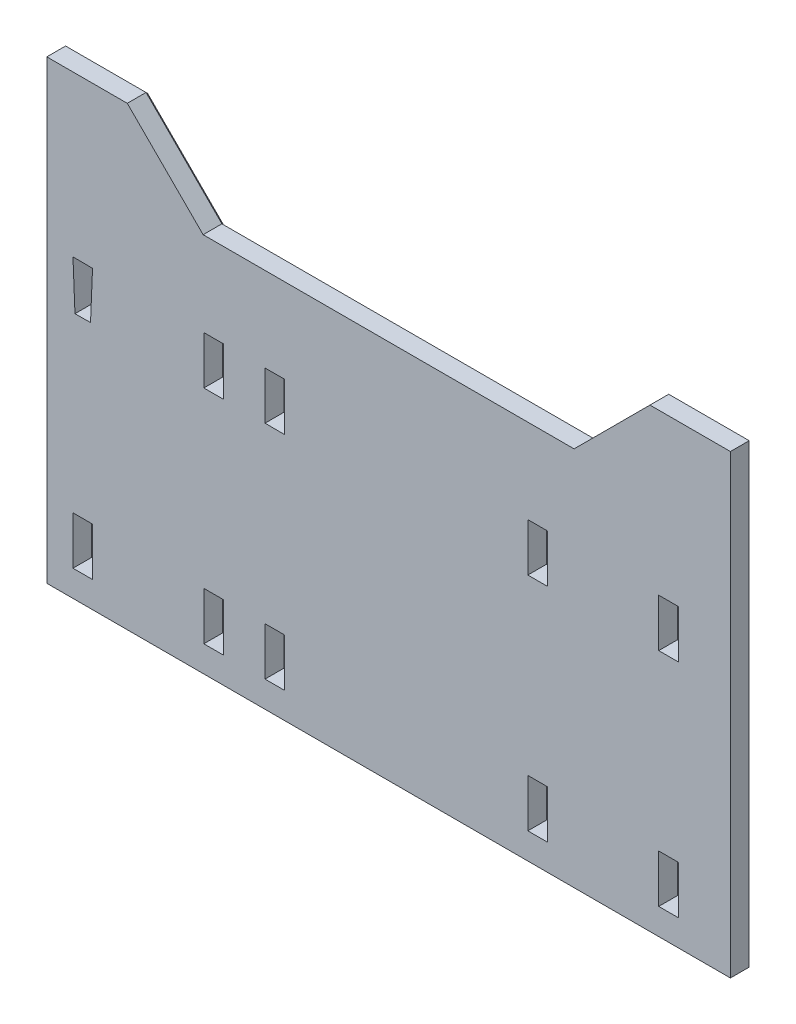
SolidWorks part; units mm, degrees
ref_plane "Front Plane" through (0, 0, 0) normal (0, 0, 1) x (1, 0, 0)
ref_plane "Top Plane" through (0, 0, 0) normal (0, 1, 0) x (1, 0, 0)
ref_plane "Right Plane" through (0, 0, 0) normal (1, 0, 0) x (0, 0, -1)
sketch "Sketch1" plane through (0, 0, 0) normal (0, 0, 1) x (1, 0, 0)
  line L6 (-34.4451, 25.1249) -> (-30.7951, 25.1249)
  line L7 (25.9549, 25.1249) -> (29.6049, 25.1249)
  line L8 (25.9549, 25.1249) -> (25.9549, 16.1751)
  line L9 (25.9549, 16.1751) -> (29.6049, 16.1751)
  line L10 (29.6049, 25.1249) -> (29.6049, 16.1751)
  line L12 (25.9549, -16.1751) -> (29.6049, -16.1751)
  line L13 (25.9549, -25.1249) -> (25.9549, -16.1751)
  line L14 (29.6049, -25.1249) -> (29.6049, -16.1751)
  line L15 (25.9549, -25.1249) -> (29.6049, -25.1249)
  line L16 (-19.3951, 25.1249) -> (-23.0451, 25.0989)
  line L17 (-19.3951, 25.1249) -> (-19.408, 16.1751)
  line L18 (-23.0451, 25.0989) -> (-23.0322, 16.2011)
  line L19 (-19.408, 16.1751) -> (-23.0322, 16.2011)
  line L20 (-19.3951, -16.1751) -> (-23.0451, -16.1751)
  line L21 (-19.3951, -25.1249) -> (-19.3951, -16.1751)
  line L22 (-23.0451, -25.1249) -> (-23.0451, -16.1751)
  line L23 (-19.3951, -25.1249) -> (-23.0451, -25.1249)
  line L39 (50.3549, 25.1249) -> (54.0049, 25.1249)
  line L40 (50.3549, 25.1249) -> (50.3549, 16.1751)
  line L41 (50.3549, 16.1751) -> (54.0049, 16.1751)
  line L42 (54.0049, 25.1249) -> (54.0049, 16.1751)
  line L43 (50.3549, -16.1751) -> (54.0049, -16.1751)
  line L44 (50.3549, -16.1751) -> (50.3549, -25.1249)
  line L45 (50.3549, -25.1249) -> (54.0049, -25.1249)
  line L46 (54.0049, -16.1751) -> (54.0049, -25.1249)
  line L47 (-34.4451, 25.1249) -> (-34.4451, 16.1751)
  line L48 (-34.4451, 16.1751) -> (-30.7951, 16.1751)
  line L49 (-30.7951, 25.1249) -> (-30.7951, 16.1751)
  line L50 (-34.4451, -16.1751) -> (-30.7951, -16.1751)
  line L51 (-34.4451, -16.1751) -> (-34.4451, -25.1249)
  line L52 (-34.4451, -25.1249) -> (-30.7951, -25.1249)
  line L53 (-30.7951, -16.1751) -> (-30.7951, -25.1249)
  line L60 (-58.8451, 25.1461) -> (-55.1951, 25.121)
  line L61 (-58.8451, 25.1461) -> (-58.4713, 16.1539)
  line L62 (-58.4713, 16.1539) -> (-55.5689, 16.179)
  line L63 (-55.1951, 25.121) -> (-55.5689, 16.179)
  line L64 (-58.8451, -16.1751) -> (-55.1951, -16.1751)
  line L65 (-58.8451, -16.1751) -> (-58.8451, -25.1249)
  line L66 (-58.8451, -25.1249) -> (-55.1951, -25.1249)
  line L67 (-55.1951, -16.1751) -> (-55.1951, -25.1249)
  line L80 (-63.7201, 30) -> (63.7201, 30)
  line L81 (63.7201, 30) -> (63.7201, -30)
  line L82 (52.1799, 25.1249) -> (52.1799, 16.1751) construction
  line L83 (27.7799, 16.1751) -> (27.7799, 25.1249) construction
  line L84 (-63.7201, 30) -> (-63.7201, -30)
  line L85 (-63.7201, -30) -> (63.7201, -30)
  line L87 (53.2799, 20.65) -> (50.3549, 20.65) construction
  line L88 (29.6049, 20.65) -> (25.9549, 20.65) construction
  line L89 (54.0049, -20.65) -> (50.3549, -20.65) construction
  line L90 (52.1799, -16.1751) -> (52.1799, -25.1249) construction
  line L91 (27.7799, -16.1751) -> (27.7799, -25.1249) construction
  line L92 (29.6049, -20.65) -> (25.9549, -20.65) construction
  line L93 (-19.3951, -20.65) -> (-23.0451, -20.65) construction
  line L94 (-21.2201, -16.1751) -> (-21.2201, -25.1249) construction
  line L95 (-32.6201, -16.1751) -> (-32.6201, -25.1249) construction
  line L96 (-30.7951, -20.65) -> (-34.4451, -20.65) construction
  line L97 (-55.1951, -20.65) -> (-58.8451, -20.65) construction
  line L98 (-57.0201, -16.1751) -> (-57.0201, -25.1249) construction
  line L99 (-57.0201, 25.1335) -> (-57.0201, 16.1665) construction
  line L100 (-32.6201, 25.1249) -> (-32.6201, 16.1751) construction
  line L101 (-21.2201, 25.1119) -> (-21.2201, 16.1881) construction
  line L102 (-55.382, 20.65) -> (-58.6582, 20.65) construction
  line L103 (-34.4451, 20.65) -> (-30.7951, 20.65) construction
  line L104 (-19.4016, 20.65) -> (-23.0386, 20.65) construction
  point P0 (0, 0)
  point P86 (0, 30)
  point P87 (63.7201, 0)
  dimension "D1" = 9
  dimension "D2" = 3.65
  dimension "D3" = 127.4402
  dimension "D4" = 60
  dimension "D7" = 11.4
  dimension "D8" = 24.4
  dimension "D5" = 27.7799
  dimension "D6" = 21.2201
  dimension "D10" = 20.65
  dimension "D11" = 20.65
  dimension "D9" = 24.4
extrude "Boss-Extrude1" add sketch "Sketch1" against normal blind 4
sketch "Sketch2" plane through (0, 0, 0) normal (0, 0, 1) x (1, 0, 0)
  line L0 (-63.7201, 30) -> (-63.7201, 55)
  line L1 (-63.7201, 55) -> (-48.7201, 55)
  line L2 (-48.7201, 55) -> (-34.578, 40.8579)
  line L7 (63.7201, 30) -> (-63.7201, 30)
  line L8 (48.7201, 55) -> (63.7201, 55)
  line L9 (63.7201, 55) -> (63.7201, 30)
  line L10 (48.7201, 55) -> (34.578, 40.8579)
  line L11 (34.578, 40.8579) -> (-34.578, 40.8579)
  line L12 (-63.7201, 30) -> (-63.7201, -30) construction
  line L14 (63.7201, -30) -> (63.7201, 30) construction
  dimension "D1" = 25
  dimension "D2" = 15
  dimension "D3" = 135
  dimension "D4" = 20
extrude "Boss-Extrude2" add sketch "Sketch2" against normal blind 4
chamfer "Chamfer1" distance 0.5 angle 45 48 edges at (56.2201, 55, -4) (41.649, 47.9289, -4) (0, 40.8579, -4) (-41.649, 47.9289, -4) (-56.2201, 55, -4) (-63.7201, 12.5, -4) (0, -30, -4) (63.7201, 12.5, -4) (29.6049, 20.65, -4) (27.7799, 16.1751, -4) (25.9549, 20.65, -4) (27.7799, 25.1249, -4) (29.6049, -20.65, -4) (27.7799, -25.1249, -4) (25.9549, -20.65, -4) (27.7799, -16.1751, -4) (-23.0386, 20.65, -4) (-21.2201, 25.1119, -4) (-19.4016, 20.65, -4) (-21.2201, 16.1881, -4) (-23.0451, -20.65, -4) (-21.2201, -16.1751, -4) (-19.3951, -20.65, -4) (-21.2201, -25.1249, -4) (-30.7951, 20.65, -4) (-32.6201, 16.1751, -4) (-34.4451, 20.65, -4) (-32.6201, 25.1249, -4) (-30.7951, -20.65, -4) (-32.6201, -25.1249, -4) (-34.4451, -20.65, -4) (-32.6201, -16.1751, -4) (54.0049, 20.65, -4) (52.1799, 16.1751, -4) (50.3549, 20.65, -4) (52.1799, 25.1249, -4) (54.0049, -20.65, -4) (52.1799, -25.1249, -4) (50.3549, -20.65, -4) (52.1799, -16.1751, -4) (-55.382, 20.65, -4) (-57.0201, 16.1665, -4) (-58.6582, 20.65, -4) (-57.0201, 25.1335, -4) (-55.1951, -20.65, -4) (-57.0201, -25.1249, -4) (-58.8451, -20.65, -4) (-57.0201, -16.1751, -4)
equation "\"pin_hole_height\"=9"
equation "\"D1@Sketch1\"=\"pin_hole_height\""
equation "\"pin_hole_width\"=3.65"
equation "\"D2@Sketch1\"=\"pin_hole_width\""
